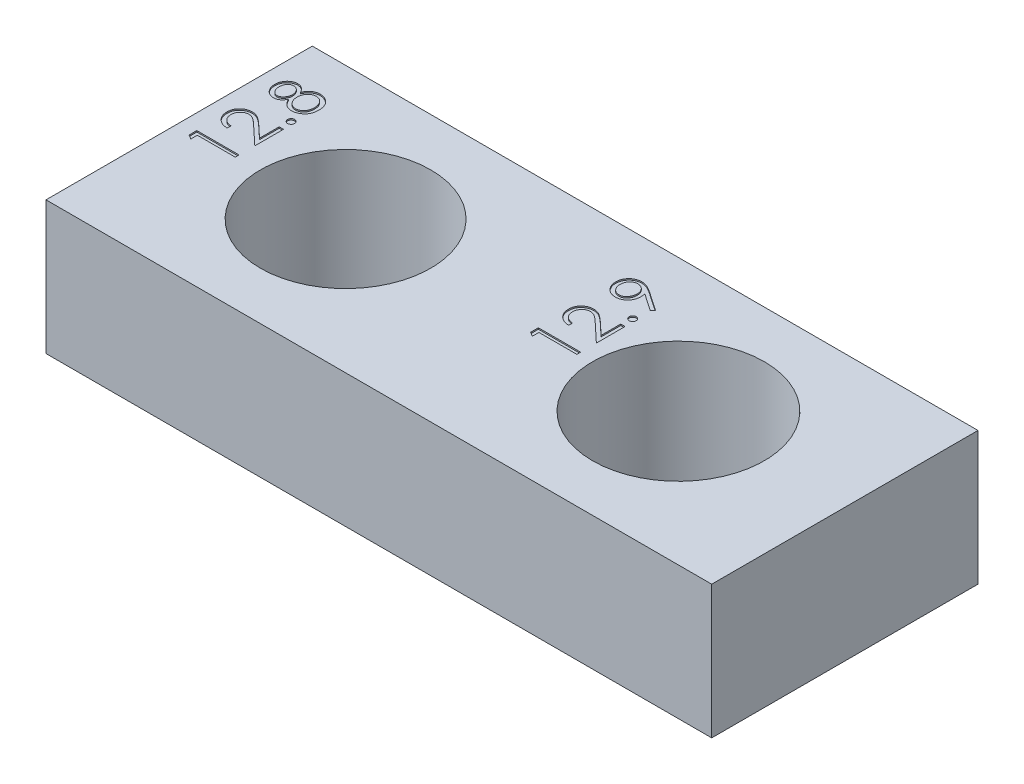
SolidWorks part; units mm, degrees
ref_plane "Front Plane" through (0, 0, 0) normal (0, 0, 1) x (1, 0, 0)
ref_plane "Top Plane" through (0, 0, 0) normal (0, 1, 0) x (1, 0, 0)
ref_plane "Right Plane" through (0, 0, 0) normal (1, 0, 0) x (0, 0, -1)
sketch "Sketch1" plane through (0, 0, 0) normal (0, 1, 0) x (1, 0, 0)
  line L0 (-12.5, 0) -> (12.5, 0) construction
  line L1 (25, -10) -> (-25, -10)
  line L2 (25, -10) -> (25, 10)
  line L3 (25, 10) -> (-25, 10)
  line L4 (-25, -10) -> (-25, 10)
  line L5 (25, -10) -> (-25, 10) construction
  line L6 (25, 10) -> (-25, -10) construction
  circle A0 centre (-12.5, 0) radius 6.4
  circle A1 centre (12.5, 0) radius 6.45
  point P0 (0, 0)
  point P11 (0, 0)
  dimension "D3" = 12.8
  dimension "D4" = 12.9
  dimension "D1" = 50
  dimension "D2" = 20
  dimension "D5" = 25
extrude "Boss-Extrude1" add sketch "Sketch1" along normal blind 10
sketch "Sketch2" plane through (0, 10, 0) normal (0, 1, 0) x (1, 0, 0)
  line L0 (-20.6679, 7.3338) -> (-20.6679, -6.828) construction
  text T0 "12.8\r\n\r\n\r\n\r\n12.9\r\n"
extrude "Cut-Extrude1" cut sketch "Sketch2" against normal blind 0.1
